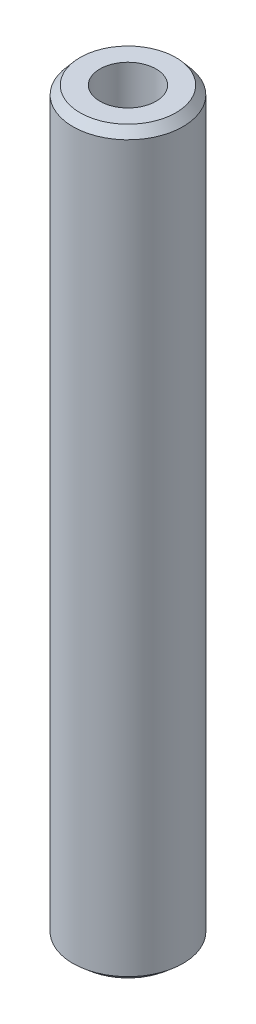
SolidWorks part; units mm, degrees
ref_plane "Front Plane" through (0, 0, 0) normal (0, 0, 1) x (1, 0, 0)
ref_plane "Top Plane" through (0, 0, 0) normal (0, 1, 0) x (1, 0, 0)
ref_plane "Right Plane" through (0, 0, 0) normal (1, 0, 0) x (0, 0, -1)
sketch "Sketch1" plane through (0, 0, 0) normal (0, 1, 0) x (1, 0, 0)
  circle A0 centre (0, 0) radius 22.5
  dimension "SHAFT_OD" = 45
extrude "Boss-Extrude1" add sketch "Sketch1" along normal blind 302.459
sketch "Sketch2" plane through (0, 0, 0) normal (0, 1, 0) x (1, 0, 0)
  circle A0 centre (0, 0) radius 11.4601
  dimension "BORE_D" = 22.9202
extrude "Cut-Extrude1" cut sketch "Sketch2" along normal through all
chamfer "Chamfer1" distance 3.4511 angle 40.302 2 edges at (0, 302.459, 22.5) (0, 0, 22.5) first distance on face at (0, 302.459, 22.5) first distance on face at (0, 0, 11.4601)
